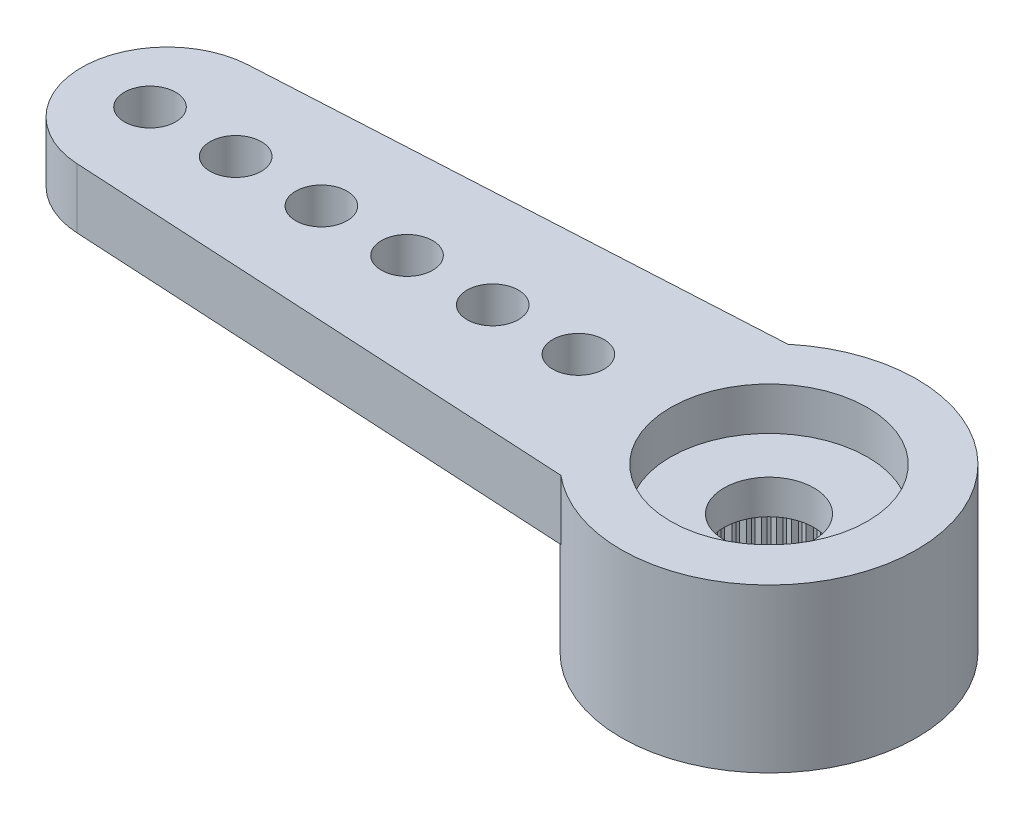
SolidWorks part; units mm, degrees
material "PVC Rígido"
ref_plane "Plano frontal" through (0, 0, 0) normal (0, 0, 1) x (1, 0, 0)
ref_plane "Plano superior" through (0, 0, 0) normal (0, 1, 0) x (1, 0, 0)
ref_plane "Plano direito" through (0, 0, 0) normal (1, 0, 0) x (0, 0, -1)
sketch "Esboço1" plane through (0, 0, 0) normal (0, 1, 0) x (1, 0, 0)
  line L0 (0, 0) -> (-14.05, 0) construction
  line L1 (-14.1591, 1.997) -> (-2.2091, 2.65)
  line L2 (-2.2091, -2.65) -> (-14.1591, -1.997)
  arc A0 (-2.2091, -2.65) -> (-2.2091, 2.65) centre (0, 0) ccw
  arc A1 (-14.1591, 1.997) -> (-14.1591, -1.997) centre (-14.05, 0) ccw
  dimension "D1" = 6.9
  dimension "D2" = 4
  dimension "D3" = 19.5
  dimension "D4" = 5.3
extrude "Ressalto-extrusão1" add sketch "Esboço1" against normal blind 1.4
sketch "Esboço2" plane through (0, -1.4, 0) normal (0, -1, 0) x (1, 0, 0)
  arc A0 (-2.2091, -2.65) -> (-2.2091, 2.65) centre (0, 0) ccw construction
  circle A1 centre (0, 0) radius 3.45
extrude "Ressalto-extrusão2" add sketch "Esboço2" along normal offset from surface (2.4 mm away) 3.8 up to face at (-7.242, 0, 0)
hole_wizard "Furo4" positions "Esboço9" profile "Esboço10" legacy end condition through all
sketch "Esboço9" plane through (0, 0, 0) normal (0, 1, 0) x (1, 0, 0)
  line L1 (-14.45, 0) -> (0, 0) construction
  arc A2 (-14.1591, 1.997) -> (-14.1591, -1.997) centre (-14.05, 0) ccw construction
  point P0 (-14.45, 0)
  point P19 (-16.05, 0)
  dimension "D1" = 1.6
sketch "Esboço10" plane through (-14.45, 0, 0) normal (1, 0, 0) x (0, 0, 1)
  line L0 (0, 0) -> (0, 3.8)
  line L1 (0, 3.8) -> (0.6, 3.8)
  line L2 (0.6, 3.8) -> (0.6, 0)
  line L3 (0.6, 0) -> (0, 0)
  line L4 (0, 110) -> (0, -10) construction
  dimension "Diameter" = 1.2
  dimension "Depth" = 3.8
pattern_linear "Padrão linear1" count 6 spacing 2 along (1, 0, 0) of "Furo4"
hole_wizard "Furo1" positions "Esboço3" profile "Esboço4" legacy
sketch "Esboço3" plane through (0, -3.8, 0) normal (0, -1, 0) x (-1, 0, 0)
  point P0 (0, 0)
sketch "Esboço4" plane through (0, -3.8, 0) normal (1, 0, 0) x (0, 0, -1)
  line L0 (0, 0) -> (0, 2)
  line L1 (0, 2) -> (2.475, 2)
  line L2 (2.475, 2) -> (2.475, 0)
  line L3 (2.475, 0) -> (0, 0)
  line L4 (0, 110) -> (0, -10) construction
  dimension "Diameter" = 4.95
  dimension "Depth" = 2
hole_wizard "Furo2" positions "Esboço5" profile "Esboço6" legacy
sketch "Esboço5" plane through (0, 0, 0) normal (0, 1, 0) x (1, 0, 0)
  point P0 (0, 0)
sketch "Esboço6" plane through (0, 0, 0) normal (1, 0, 0) x (0, 0, 1)
  line L0 (0, 0) -> (0, 1)
  line L1 (0, 1) -> (2.3, 1)
  line L2 (2.3, 1) -> (2.3, 0)
  line L3 (2.3, 0) -> (0, 0)
  line L4 (0, 110) -> (0, -10) construction
  dimension "Diameter" = 4.6
  dimension "Depth" = 1
hole_wizard "Furo3" positions "Esboço7" profile "Esboço8" legacy end condition through all
sketch "Esboço7" plane through (0, 0, 0) normal (0, 1, 0) x (1, 0, 0)
  point P0 (0, 0)
sketch "Esboço8" plane through (0, 0, 0) normal (1, 0, 0) x (0, 0, 1)
  line L0 (0, 0) -> (0, 3.8)
  line L1 (0, 3.8) -> (1.05, 3.8)
  line L2 (1.05, 3.8) -> (1.05, 0)
  line L3 (1.05, 0) -> (0, 0)
  line L4 (0, 110) -> (0, -10) construction
  dimension "Diameter" = 2.1
  dimension "Depth" = 3.8
sketch "Esboço11" plane through (0, -3.8, 0) normal (0, -1, 0) x (1, 0, 0)
  line L0 (-0.0981, 2.4731) -> (0, 2.375)
  line L1 (0, 2.375) -> (0.0981, 2.4731)
  line L2 (0, 0) -> (0, 2.475) construction
  circle A0 centre (0, 0) radius 2.375 construction
  circle A1 centre (0, 0) radius 2.475
  arc A2 (0.0981, 2.4731) -> (-0.0981, 2.4731) centre (0, 0) ccw
  dimension "D3" = 4.75
  dimension "D2" = 0.1
  dimension "D1" = 0
extrude "Ressalto-extrusão3" add sketch "Esboço11" against normal up to surface (2 mm away) up to face at (0, -1.8, 1.05)
pattern_circular "PadrãoCircular1" count 60 over 360 about axis through (0, -1.4, 0) along (0, 1, 0) of "Ressalto-extrusão3"
